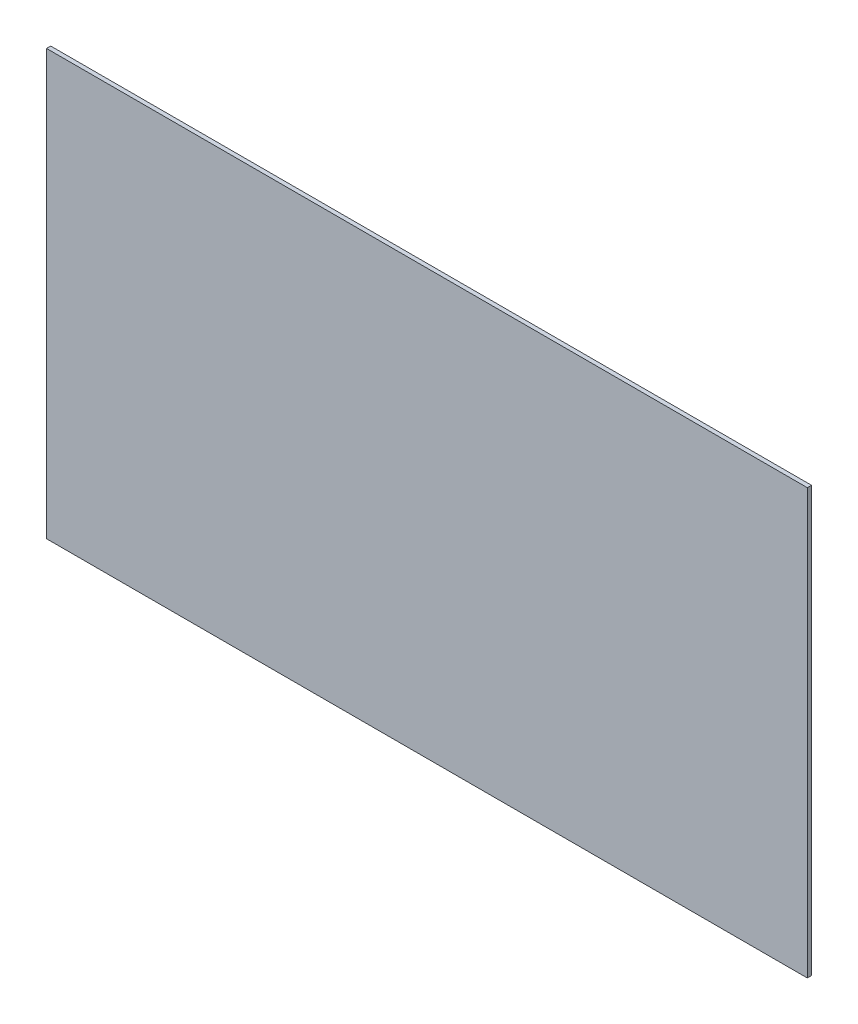
SolidWorks part; units mm, degrees
ref_plane "Front Plane" through (0, 0, 0) normal (0, 0, 1) x (1, 0, 0)
ref_plane "Top Plane" through (0, 0, 0) normal (0, 1, 0) x (1, 0, 0)
ref_plane "Right Plane" through (0, 0, 0) normal (1, 0, 0) x (0, 0, -1)
sketch "PlayField" plane through (0, 0, 0) normal (0, 0, 1) x (1, 0, 0)
  line L0 (0, 0) -> (0, 99.0314) construction
  line L1 (-254, 133.35) -> (254, 133.35)
  line L2 (-254, 133.35) -> (-254, -133.35)
  line L3 (-254, -133.35) -> (254, -133.35)
  line L4 (254, 133.35) -> (254, -133.35)
  line L5 (-254, 133.35) -> (254, -133.35) construction
  line L6 (-254, -133.35) -> (254, 133.35) construction
  circle A0 centre (-218.44, 0) radius 18.415
  circle A1 centre (218.44, 0) radius 18.415
  point P0 (0, 0)
  dimension "D3" = 36.83
  dimension "D1" = 266.7
  dimension "D2" = 508
  dimension "D4" = 35.56
sketch "Outer Boundary" plane through (0, 0, 0) normal (0, 0, 1) x (1, 0, 0)
  line L0 (-254, 133.35) -> (-254, -133.35) construction
  line L1 (-273.05, 152.4) -> (273.05, 152.4)
  line L2 (-273.05, 152.4) -> (-273.05, -152.4)
  line L3 (-273.05, -152.4) -> (273.05, -152.4)
  line L4 (273.05, 152.4) -> (273.05, -152.4)
  line L5 (-273.05, 152.4) -> (273.05, -152.4) construction
  line L6 (-273.05, -152.4) -> (273.05, 152.4) construction
  line L7 (-254, 133.35) -> (254, 133.35) construction
  point P0 (0, 0)
  dimension "D1" = 19.05
  dimension "D2" = 19.05
extrude "Boss-Extrude1" add sketch "PlayField" along normal blind 3
extrude "Boss-Extrude2" add sketch "Outer Boundary" against normal blind 3
extrude "Cut-Extrude1" cut sketch "PlayField<2>" against normal through all both and the other way through all contours A0 | A1 region at (-218.44, 0, 0) region at (218.44, 0, 0)
sketch "PlayField<2>" plane through (0, 0, 0) normal (0, 0, 1) x (1, 0, 0) same geometry as "PlayField"
extrude "Cut-Extrude2" cut sketch "PlayField<3>" along normal blind 3
sketch "PlayField<3>" plane through (0, 0, 0) normal (0, 0, 1) x (1, 0, 0) same geometry as "PlayField"
sketch "Sketch1" plane through (0, 0, 0) normal (0, 0, 1) x (1, 0, 0)
  circle A0 centre (-218.44, 0) radius 18.415
  circle A1 centre (218.44, 0) radius 18.415
  circle A2 centre (-218.44, 0) radius 18.415 construction
extrude "Boss-Extrude3" add sketch "Sketch1" against normal blind 3
sketch "Sketch2" [suppressed] plane through (0, 0, 3) normal (0, 0, 1) x (1, 0, 0)
  line L0 (0, 133.35) -> (0, -133.35) construction
  line L1 (254, 133.35) -> (-254, 133.35) construction
  line L2 (-254, -133.35) -> (254, -133.35) construction
sketch "Sketch3" plane through (0, 0, 0) normal (0, 0, 1) x (1, 0, 0)
  line L0 (0, 152.4) -> (0, -152.4) construction
  line L1 (273.05, 152.4) -> (-273.05, 152.4) construction
  line L2 (-273.05, -152.4) -> (273.05, -152.4) construction
  line L3 (273.05, 133.35) -> (254, 152.4) construction
  line L4 (273.05, -152.4) -> (273.05, 152.4) construction
  line L5 (273.05, 0) -> (-273.05, 0) construction
  line L6 (-273.05, 152.4) -> (-273.05, -152.4) construction
  line L12 (-31.75, 152.4) -> (-12.7, 152.4)
  line L17 (-31.75, 152.4) -> (-31.75, 133.35)
  line L18 (-31.75, 133.35) -> (-12.7, 133.35)
  line L19 (-273.05, -133.35) -> (-254, -133.35)
  line L20 (-273.05, -133.35) -> (-273.05, -152.4)
  line L21 (-273.05, -152.4) -> (-254, -152.4)
  line L22 (-254, -133.35) -> (-254, -152.4)
  line L23 (-273.05, -133.35) -> (-254, -152.4) construction
  line L24 (-273.05, -152.4) -> (-254, -133.35) construction
  line L25 (-273.05, 152.4) -> (-254, 152.4)
  line L26 (-273.05, 152.4) -> (-273.05, 133.35)
  line L27 (-273.05, 133.35) -> (-254, 133.35)
  line L28 (-254, 152.4) -> (-254, 133.35)
  line L29 (-273.05, 152.4) -> (-254, 133.35) construction
  line L30 (-273.05, 133.35) -> (-254, 152.4) construction
  line L31 (273.05, 152.4) -> (254, 133.35) construction
  line L32 (273.05, -152.4) -> (254, -133.35) construction
  line L33 (273.05, -133.35) -> (254, -152.4) construction
  line L34 (254, 152.4) -> (254, 133.35)
  line L35 (273.05, 133.35) -> (254, 133.35)
  line L36 (273.05, 152.4) -> (273.05, 133.35)
  line L37 (273.05, 152.4) -> (254, 152.4)
  line L38 (254, -133.35) -> (254, -152.4)
  line L39 (273.05, -152.4) -> (254, -152.4)
  line L40 (273.05, -133.35) -> (273.05, -152.4)
  line L41 (273.05, -133.35) -> (254, -133.35)
  line L50 (-12.7, 152.4) -> (-12.7, 133.35)
  line L51 (12.7, 152.4) -> (31.75, 152.4)
  line L52 (12.7, 152.4) -> (12.7, 133.35)
  line L53 (12.7, 133.35) -> (31.75, 133.35)
  line L54 (31.75, 152.4) -> (31.75, 133.35)
  line L55 (-31.75, -152.4) -> (-12.7, -152.4)
  line L56 (-31.75, -152.4) -> (-31.75, -133.35)
  line L57 (-31.75, -133.35) -> (-12.7, -133.35)
  line L58 (-12.7, -152.4) -> (-12.7, -133.35)
  line L59 (12.7, -133.35) -> (31.75, -133.35)
  line L60 (12.7, -133.35) -> (12.7, -152.4)
  line L61 (12.7, -152.4) -> (31.75, -152.4)
  line L62 (31.75, -133.35) -> (31.75, -152.4)
  point P13 (9.525, 142.875)
  point P22 (-263.525, -142.875)
  point P27 (-263.525, 142.875)
  point P42 (263.525, 142.875)
  point P43 (263.525, -142.875)
  dimension "D1" = 19.05
  dimension "D2" = 25.4
sketch "Sketch4" [suppressed] plane through (0, 0, 3) normal (0, 0, 1) x (1, 0, 0)
  line L0 (-254, 133.35) -> (-254, -133.35) construction
  line L1 (-289.56, 12.7) -> (-218.44, 12.7)
  line L2 (-289.56, 12.7) -> (-289.56, -12.7)
  line L3 (-289.56, -12.7) -> (-218.44, -12.7)
  line L4 (-218.44, 12.7) -> (-218.44, -12.7)
  line L5 (-289.56, 12.7) -> (-218.44, -12.7) construction
  line L6 (-289.56, -12.7) -> (-218.44, 12.7) construction
  circle A1 centre (-218.44, 0) radius 26.415
  circle A2 centre (-218.44, 0) radius 18.415 construction
  point P0 (-254, 0)
  point P9 (-218.44, 0)
  dimension "D2" = 8
  dimension "D1" = 25.4
extrude "Cut-Extrude3" [suppressed] cut sketch "Sketch4" against normal through all both and the other way through all contours A1 | L2 L3 L4 L1
mirror "Mirror1" [suppressed] about plane through (0, 0, 0) normal (1, 0, 0)
sketch "Sketch5" [suppressed] plane through (0, 0, 3) normal (0, 0, 1) x (1, 0, 0)
  circle A0 centre (-218.44, 0) radius 38.415
  circle A1 centre (-218.44, 0) radius 18.415 construction
  circle A2 centre (218.44, 0) radius 38.415
  dimension "D1" = 20
